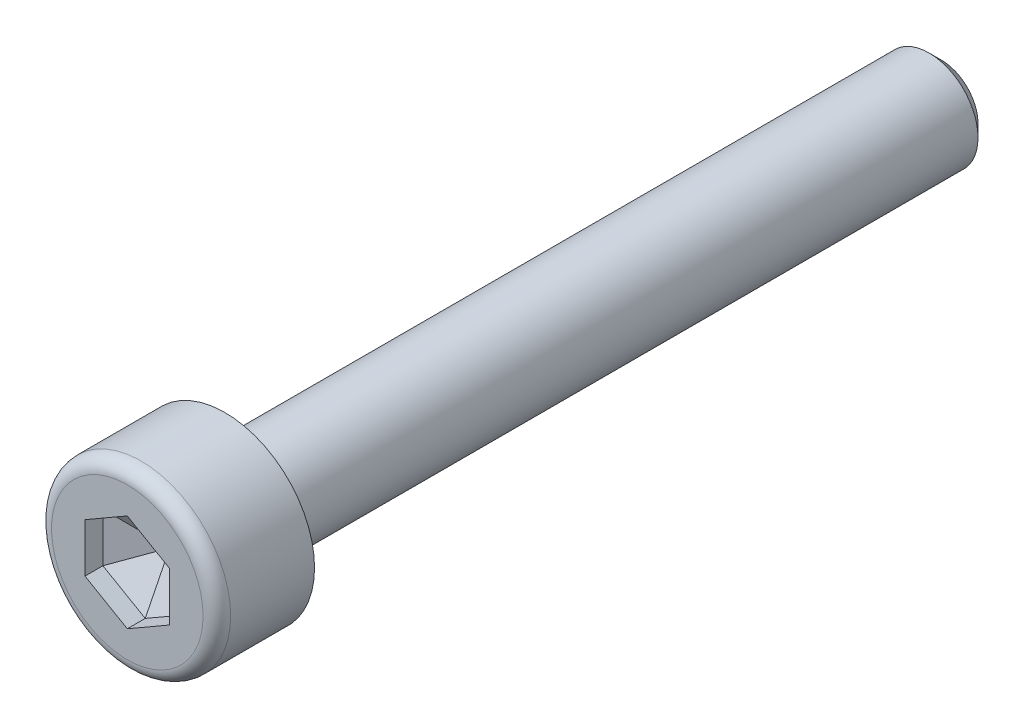
SolidWorks part; units mm, degrees
material "普通碳钢"
ref_plane "前视基准面" through (0, 0, 0) normal (0, 0, 1) x (1, 0, 0)
ref_plane "上视基准面" through (0, 0, 0) normal (0, 1, 0) x (1, 0, 0)
ref_plane "右视基准面" through (0, 0, 0) normal (1, 0, 0) x (0, 0, -1)
sketch "草图1" plane through (0, 0, 0) normal (0, 0, 1) x (1, 0, 0)
  circle A0 centre (0, 0) radius 2.75
  dimension "dk" = 5.5
extrude "凸台-拉伸1" add sketch "草图1" along normal blind 3
ref_axis "基准轴1" through (0, 0, 3) along (0, 0, -1)
sketch "草图2" plane through (0, 0, 3) normal (0, 0, 1) x (1, 0, 0)
  line L1 (1.3, 0.7506) -> (0, 1.5011)
  line L2 (0, 1.5011) -> (-1.3, 0.7506)
  line L3 (-1.3, 0.7506) -> (-1.3, -0.7506)
  line L4 (-1.3, -0.7506) -> (0, -1.5011)
  line L5 (0, -1.5011) -> (1.3, -0.7506)
  line L6 (1.3, -0.7506) -> (1.3, 0.7506)
  circle A0 centre (0, 0) radius 1.3 construction
  dimension "s" = 2.6
extrude "切除-拉伸1" cut sketch "草图2" against normal blind 1.3
sketch "草图3" plane through (0, 0, 0) normal (0, 0, -1) x (-1, 0, 0)
  circle A0 centre (0, 0) radius 1.5
  dimension "d" = 3
extrude "凸台-拉伸2" add sketch "草图3" along normal blind 22
cosmetic thread "装饰螺纹线1" parameters "b"=4.9, "D2"=1.221
chamfer "倒角1" distance 0.375 angle 45 1 edges at (-1.5, 0, -22)
fillet "圆角1" radius 0.4231 1 edges at (2.75, 0, 3)
chamfer "倒角2" distance 0.7493 angle 60 6 edges at (-1.3, 0, 1.7) (-0.65, 1.1258, 1.7) (0.65, 1.1258, 1.7) (1.3, 0, 1.7) (-0.65, -1.1258, 1.7) (0.65, -1.1258, 1.7) first distance on face at (-1.3, 0, 2.35) first distance on face at (-0.65, 1.1258, 2.35) first distance on face at (0.65, 1.1258, 2.35) first distance on face at (1.3, 0, 2.35) first distance on face at (-0.65, -1.1258, 2.35) first distance on face at (0.65, -1.1258, 2.35)
fillet "圆角2" radius 0.1 1 edges at (1.5, 0, 0)
ref_plane "基准面1" through (0, 0, 0) normal (0, 0, -1) x (-1, 0, 0)
equation "\"D1@倒角2\" = \"s@草图2\" / 3.47"
equation "\"D1@圆角1\"= \"dk@草图1\" / 13"
equation "\"D1@倒角1\"= \"d@草图3\" / 8"
equation "\"D1@圆角2\"= \"d@草图3\" / \"d@草图3\" * 0.1"
